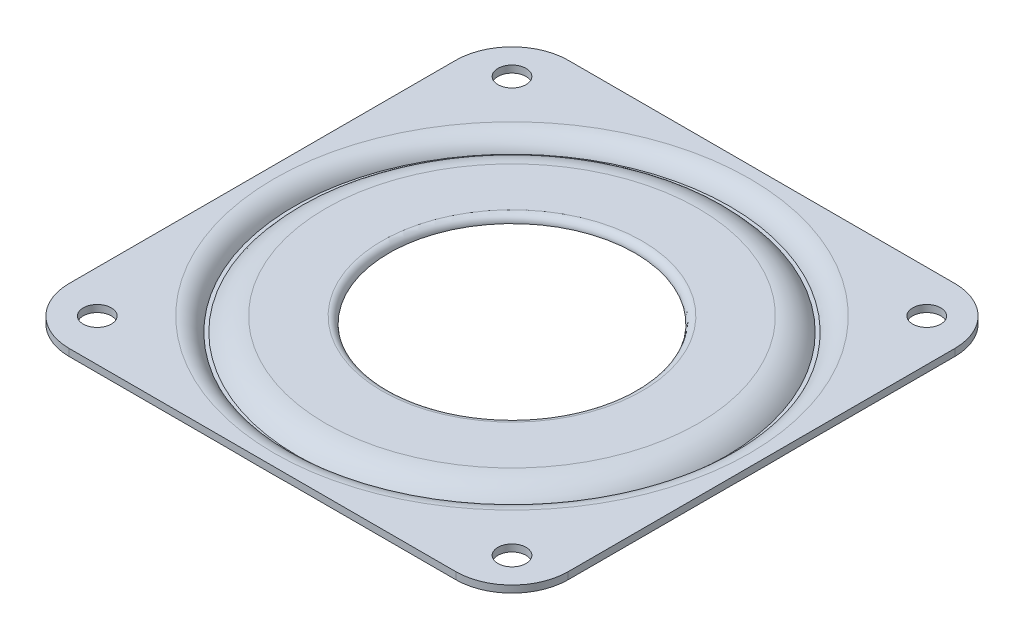
SolidWorks part; units mm, degrees
ref_plane "Front Plane" through (0, 0, 0) normal (0, 0, 1) x (1, 0, 0)
ref_plane "Top Plane" through (0, 0, 0) normal (0, 1, 0) x (1, 0, 0)
ref_plane "Right Plane" through (0, 0, 0) normal (1, 0, 0) x (0, 0, -1)
sketch "Sketch1" plane through (0, 0, 0) normal (0, 1, 0) x (1, 0, 0)
  line L1 (0, 0) -> (71, 0)
  line L2 (0, 0) -> (0, 71)
  line L3 (0, 71) -> (71, 71)
  line L4 (71, 0) -> (71, 71)
  circle A0 centre (6, 6) radius 2
  circle A1 centre (65, 6) radius 2
  circle A2 centre (65, 65) radius 2
  circle A3 centre (6, 65) radius 2
  circle A4 centre (35.5, 35.5) radius 17.5
  dimension "D3" = 4
  dimension "D10" = 35
  dimension "D1" = 71
  dimension "D2" = 71
  dimension "D4" = 6
  dimension "D5" = 6
  dimension "D8" = 35.5
  dimension "D9" = 35.5
  dimension "D11" = 6
  dimension "D12" = 6
  dimension "D13" = 6
  dimension "D14" = 6
  dimension "D6" = 2
  dimension "D7" = 2
extrude "Boss-Extrude1" add sketch "Sketch1" along normal blind 3
fillet "Fillet2" radius 8 4 edges at (0, 1.5, -71) (0, 1.5, 0) (71, 1.5, -71) (71, 1.5, 0)
sketch "Sketch2" plane through (0, 3, 0) normal (0, 1, 0) x (1, 0, 0)
  circle A0 centre (35.5, 35.5) radius 31
  circle A1 centre (35.5, 35.5) radius 30.5
  dimension "D1" = 62
  dimension "D2" = 61
extrude "Cut-Extrude1" cut sketch "Sketch2" against normal blind 2
fillet "Fillet3" radius 5 1 edges at (35.5, 3, -5)
fillet "Fillet4" radius 3 1 edges at (35.5, 3, -4.5)
fillet "Fillet5" radius 1 1 edges at (35.5, 3, -18)
sketch "Sketch4" plane through (0, 0, 0) normal (0, -1, 0) x (-1, 0, 0)
  line L1 (5.9211, -3.665) -> (-74.1236, -3.665)
  line L2 (5.9211, -3.665) -> (5.9211, 74.3943)
  line L3 (5.9211, 74.3943) -> (-74.1236, 74.3943)
  line L4 (-74.1236, -3.665) -> (-74.1236, 74.3943)
  circle A0 centre (-35.5, 35.5) radius 32.5
  circle A1 centre (-35.5, 35.5) radius 29
  dimension "D1" = 65
  dimension "D2" = 58
extrude "Cut-Extrude4" cut sketch "Sketch4" against normal blind 2
fillet "Fillet8" radius 4 1 edges at (35.5, 2, -64.5)
fillet "Fillet9" radius 4 1 edges at (35.5, 2, -68)
